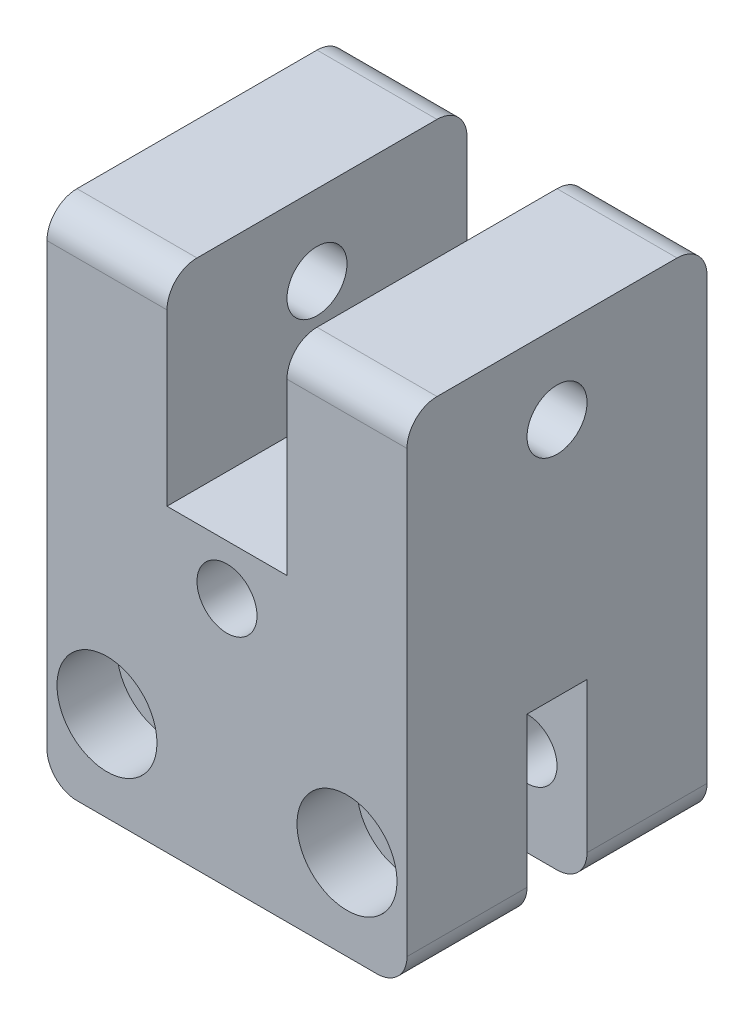
SolidWorks part; units mm, degrees
ref_plane "Alzado" through (0, 0, 0) normal (0, 0, 1) x (1, 0, 0)
ref_plane "Planta" through (0, 0, 0) normal (0, 1, 0) x (1, 0, 0)
ref_plane "Vista lateral" through (0, 0, 0) normal (1, 0, 0) x (0, 0, -1)
sketch "Croquis2" plane through (0, 0, 0) normal (0, 0, 1) x (1, 0, 0)
  line L1 (-9, 7.5) -> (9, 7.5)
  line L2 (-9, 7.5) -> (-9, -7.5)
  line L3 (-9, -7.5) -> (9, -7.5)
  line L4 (9, 7.5) -> (9, -7.5)
  point P4 (0, -7.5)
  point P6 (9, 0)
  dimension "D1" = 18
  dimension "D2" = 15
extrude "Saliente-Extruir1" add sketch "Croquis2" along normal mid plane 15
sketch "Croquis3" plane through (0, 0, 0) normal (0, 0, 1) x (1, 0, 0)
  line L0 (-9, 7.5) -> (-9, -7.5) construction
  line L1 (-9, 1.5) -> (9, 1.5)
  line L2 (-9, 1.5) -> (-9, -7.5)
  line L3 (-9, -7.5) -> (9, -7.5)
  line L4 (9, 1.5) -> (9, -7.5)
  dimension "D1" = 9
extrude "Cortar-Extruir1" cut sketch "Croquis3" against normal mid plane 3
sketch "Croquis4" plane through (0, 0, 0) normal (0, 0, 1) x (1, 0, 0)
  line L1 (-1.5, -3) -> (-1.5, -7.5)
  line L2 (-9, -7.5) -> (9, -7.5) construction
  line L3 (1.5, -3) -> (1.5, -7.5)
  line L4 (-1.5, -7.5) -> (1.5, -7.5)
  line L5 (9, 1.5) -> (-9, 1.5) construction
  arc A0 (1.5, -3) -> (-1.5, -3) centre (0, -3) ccw
  point P4 (0, -1.5)
  dimension "D2" = 3
  dimension "D1" = 3
extrude "Cortar-Extruir2" cut sketch "Croquis4" against normal through all
sketch "Croquis10" plane through (0, 7.5, 0) normal (0, 1, 0) x (1, 0, 0)
  line L0 (-3, 7.5) -> (-3, -7.5)
  line L1 (3, 7.5) -> (3, -7.5)
  line L2 (0, 7.5) -> (0, -7.5) construction
  line L3 (-3, 7.5) -> (-9, 7.5)
  line L4 (9, 7.5) -> (-9, 7.5)
  line L5 (-9, 7.5) -> (-9, -7.5)
  line L6 (-9, -7.5) -> (9, -7.5)
  line L7 (9, -7.5) -> (9, 7.5)
  line L8 (9, 7.5) -> (3, 7.5)
  line L9 (-9, 7.5) -> (-9, -7.5)
  line L10 (-9, -7.5) -> (-3, -7.5)
  line L11 (9, -7.5) -> (9, 7.5)
  line L12 (3, -7.5) -> (9, -7.5)
  line L13 (9, 7.5) -> (-9, 7.5) construction
  point P11 (0, 0)
  dimension "D2" = 6
  dimension "D1" = 0
extrude "Saliente-Extruir4" add sketch "Croquis10" along normal blind 10
sketch "Croquis7" plane through (0, 0, 0) normal (1, 0, 0) x (0, 0, -1)
  line L1 (-7.5, 17.5) -> (7.5, 17.5) construction
  circle A0 centre (0, 13.5) radius 1.5
  dimension "D1" = 3
  dimension "D2" = 4
extrude "Cortar-Extruir3" cut sketch "Croquis7" against normal through all both and the other way through all
sketch "Croquis11" plane through (0, 0, 0) normal (0, 0, 1) x (1, 0, 0)
  line L0 (6, 17.5) -> (6, -7.5) construction
  line L1 (9, 17.5) -> (3, 17.5) construction
  line L2 (1.5, -7.5) -> (9, -7.5) construction
  line L3 (-6, 17.5) -> (-6, -7.5) construction
  line L4 (-3, 17.5) -> (-9, 17.5) construction
  line L5 (-9, -7.5) -> (-1.5, -7.5) construction
  line L6 (6, -3) -> (-6, -3) construction
  circle A0 centre (6, -3) radius 1.5
  circle A1 centre (-6, -3) radius 1.5
  point P16 (0, 0)
  point P18 (0, 0)
  dimension "D2" = 3
  dimension "D1" = 4.5
extrude "Cortar-Extruir4" cut sketch "Croquis11" against normal through all both and the other way through all
sketch "Croquis13" plane through (0, 0, -7.5) normal (0, 0, -1) x (-1, 0, 0)
  circle A0 centre (-6, -3) radius 2.5
  circle A1 centre (6, -3) radius 2.5
  dimension "D1" = 5
extrude "Cortar-Extruir5" cut sketch "Croquis13" against normal blind 3
sketch "Croquis14" plane through (0, 0, 7.5) normal (0, 0, 1) x (1, 0, 0)
  circle A0 centre (-6, -3) radius 2.5
  circle A1 centre (6, -3) radius 2.5
  dimension "D1" = 5
extrude "Cortar-Extruir6" cut sketch "Croquis14" against normal blind 3
fillet "Redondeo2" radius 1.5 4 edges at (-6, 17.5, 7.5) (6, 17.5, 7.5) (-6, 17.5, -7.5) (6, 17.5, -7.5)
fillet "Redondeo3" radius 1.5 4 edges at (-9, -7.5, -4.5) (-9, -7.5, 4.5) (9, -7.5, -4.5) (9, -7.5, 4.5)
sketch "Croquis15" plane through (0, 0, 7.5) normal (0, 0, 1) x (1, 0, 0)
  circle A0 centre (0, 5) radius 1.5
  point P2 (0, 0)
  point P4 (0, 0)
  point P5 (0, 0)
  point P7 (14.7921, 4.2836)
  dimension "D2" = 3
  dimension "D1" = 5
extrude "Cortar-Extruir7" cut sketch "Croquis15" against normal blind 10
